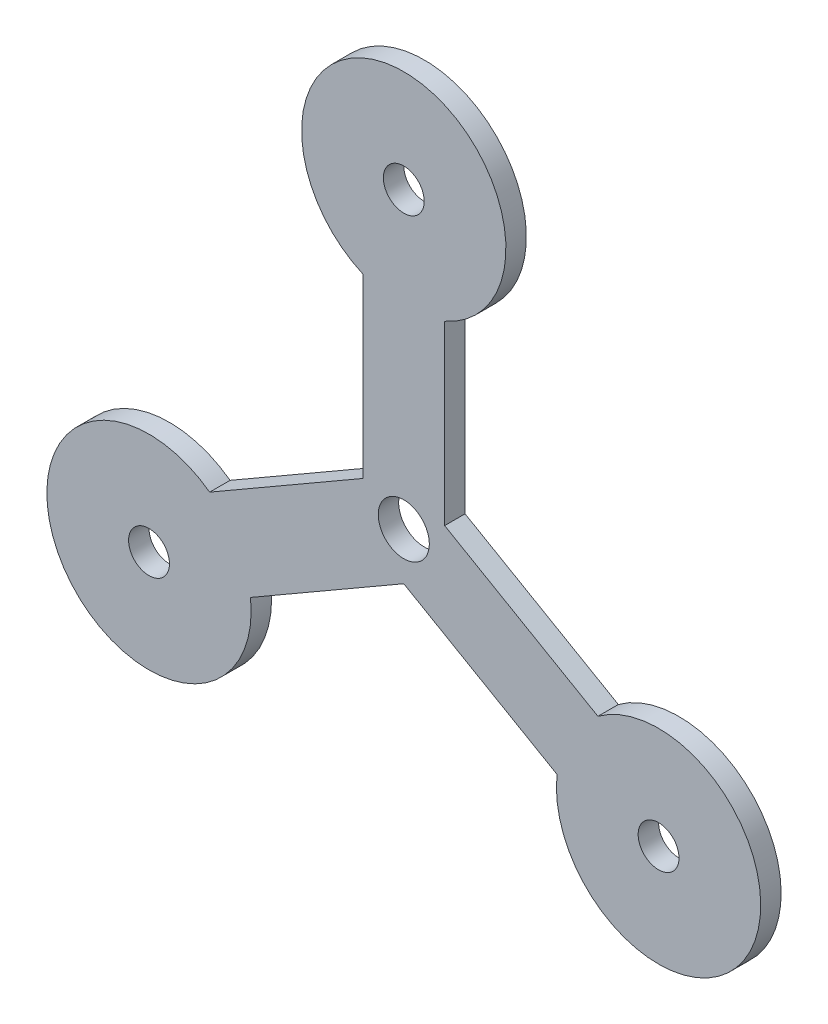
SolidWorks part; units mm, degrees
ref_plane "Front Plane" through (0, 0, 0) normal (0, 0, 1) x (1, 0, 0)
ref_plane "Top Plane" through (0, 0, 0) normal (0, 1, 0) x (1, 0, 0)
ref_plane "Right Plane" through (0, 0, 0) normal (1, 0, 0) x (0, 0, -1)
sketch "Sketch1" plane through (0, 0, 0) normal (0, 0, 1) x (1, 0, 0)
  line L0 (0, 0) -> (0, 144) construction
  line L1 (20, 144) -> (-20, 144)
  line L6 (0, 0) -> (124.7077, -72) construction
  line L7 (0, 0) -> (-124.7077, -72) construction
  line L8 (114.7077, -89.3205) -> (134.7077, -54.6795)
  line L9 (-114.7077, -89.3205) -> (-134.7077, -54.6795)
  line L10 (-134.7077, -54.6795) -> (-20, 11.547)
  line L11 (-20, 11.547) -> (-20, 144)
  line L12 (20, 144) -> (20, 11.547)
  line L13 (20, 11.547) -> (134.7077, -54.6795)
  line L14 (114.7077, -89.3205) -> (0, -23.094)
  line L15 (0, -23.094) -> (-114.7077, -89.3205)
  point P6 (0, 144)
  point P10 (0, 0)
  point P12 (124.7077, -72)
  point P15 (-124.7077, -72)
  dimension "D1" = 3
extrude "Boss-Extrude2" add sketch "Sketch1" along normal blind 10
sketch "Sketch3" plane through (0, 0, 10) normal (0, 0, 1) x (1, 0, 0)
  line L0 (-134.7077, -54.6795) -> (-114.7077, -89.3205) construction
  circle A0 centre (-124.7077, -72) radius 50
  circle A1 centre (0, 144) radius 50
  circle A2 centre (124.7077, -72) radius 50
  point P11 (0, 0)
  dimension "D1" = 3
extrude "Boss-Extrude3" add sketch "Sketch3" against normal blind 10
sketch "Sketch4" plane through (0, 0, 10) normal (0, 0, 1) x (1, 0, 0)
  circle A1 centre (0, 144) radius 10
  circle A2 centre (124.7077, -72) radius 10
  circle A3 centre (-124.7077, -72) radius 10
  point P9 (0, 0)
  dimension "D1" = 3
extrude "Boss-Extrude4" add sketch "Sketch4" along normal blind 90
sketch "Sketch5" plane through (0, 0, 100) normal (0, 0, 1) x (1, 0, 0)
  circle A0 centre (0, 144) radius 10
extrude "Cut-Extrude1" cut sketch "Sketch5" against normal blind 30
sketch "Sketch6" plane through (0, 0, 10) normal (0, 0, 1) x (1, 0, 0)
  circle A0 centre (0, 0) radius 13
extrude "Cut-Extrude2" cut sketch "Sketch6" against normal blind 10
sketch "Sketch7" plane through (0, 0, 70) normal (0, 0, 1) x (1, 0, 0)
  circle A0 centre (0, 144) radius 10
extrude "Boss-Extrude5" add sketch "Sketch7" along normal blind 30
sketch "Sketch8" plane through (0, 0, 10) normal (0, 0, 1) x (1, 0, 0)
  circle A0 centre (0, 0) radius 20.3692
extrude "Boss-Extrude6" add sketch "Sketch8" against normal blind 10
sketch "Sketch9" plane through (0, 0, 100) normal (0, 0, 1) x (1, 0, 0)
  circle A0 centre (-124.7077, -72) radius 10
  circle A1 centre (0, 144) radius 10
  circle A2 centre (124.7077, -72) radius 10
  point P10 (0, 0)
  dimension "D1" = 3
extrude "Cut-Extrude3" cut sketch "Sketch9" against normal blind 100
sketch "Sketch10" plane through (0, 0, 10) normal (0, 0, 1) x (1, 0, 0)
  circle A0 centre (0, 0) radius 10
extrude "Cut-Extrude4" cut sketch "Sketch10" against normal blind 10
sketch "Sketch11" plane through (0, 0, 10) normal (0, 0, 1) x (1, 0, 0)
  circle A0 centre (0, 0) radius 12.5
extrude "Cut-Extrude5" cut sketch "Sketch11" against normal blind 10
